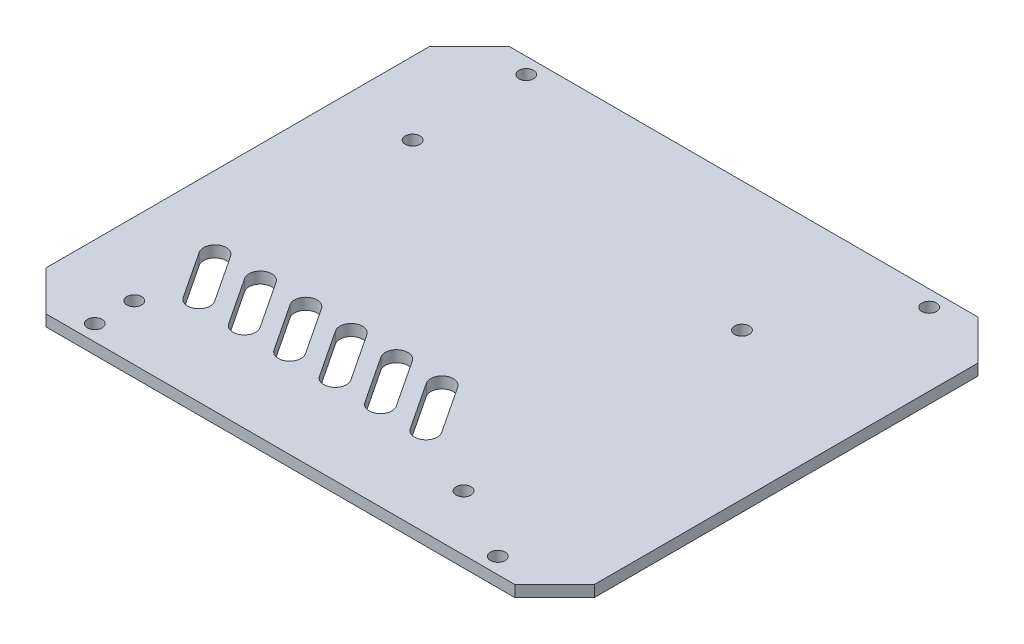
SolidWorks part; units mm, degrees
ref_plane "前视基准面" through (0, 0, 0) normal (0, 0, 1) x (1, 0, 0)
ref_plane "上视基准面" through (0, 0, 0) normal (0, 1, 0) x (1, 0, 0)
ref_plane "右视基准面" through (0, 0, 0) normal (1, 0, 0) x (0, 0, -1)
sketch "草图1" plane through (0, -18.39, 0) normal (0, -1, 0) x (1, 0, 0)
  line L16 (-51.8, -40.2958) -> (-44.7958, -47.3)
  line L17 (-44.7958, -47.3) -> (37.7958, -47.3)
  line L18 (37.7958, -47.3) -> (44.8, -40.2958)
  line L19 (44.8, -40.2958) -> (44.8, 27.2958)
  line L20 (44.8, 27.2958) -> (37.7958, 34.3)
  line L21 (-51.8, 27.2958) -> (-51.8, -40.2958)
  line L22 (37.7958, 34.3) -> (-44.7958, 34.3)
  line L23 (-44.7958, 34.3) -> (-51.8, 27.2958)
  line L24 (-51.8, -40.2958) -> (-44.7958, -47.3)
  line L25 (-44.7958, -47.3) -> (37.7958, -47.3)
  line L26 (37.7958, -47.3) -> (44.8, -40.2958)
  line L27 (44.8, -40.2958) -> (44.8, 27.2958)
  line L28 (44.8, 27.2958) -> (37.7958, 34.3)
  line L29 (-51.8, 27.2958) -> (-51.8, -40.2958)
  line L30 (37.7958, 34.3) -> (-44.7958, 34.3)
  line L31 (-44.7958, 34.3) -> (-51.8, 27.2958)
  dimension "D2" = 96.6
  dimension "D3" = 81.6
  dimension "D1" = 0.2
extrude "凸台-拉伸1" add sketch "草图1" along normal blind 2
sketch "草图2" plane through (0, -20.39, 0) normal (0, -1, 0) x (1, 0, 0)
  circle A0 centre (-39.0116, -24.5) radius 1.3
  circle A1 centre (19, -24.5) radius 1.3
  circle A2 centre (-39.0116, 24.5352) radius 1.3
  circle A3 centre (19, 24.5352) radius 1.3
  dimension "D1" = 2.6
extrude "切除-拉伸1" cut sketch "草图2" against normal up to next
sketch "草图3" plane through (0, -20.39, 0) normal (0, -1, 0) x (1, 0, 0)
  circle A0 centre (32, -44.5) radius 1.3 construction
  circle A1 centre (-39, -44.5) radius 1.3 construction
  circle A2 centre (32, 31.5) radius 1.3 construction
  circle A3 centre (-39, 31.5) radius 1.3 construction
  circle A4 centre (32, -44.5) radius 1.3
  circle A5 centre (-39, -44.5) radius 1.3
  circle A6 centre (32, 31.5) radius 1.3
  circle A7 centre (-39, 31.5) radius 1.3
extrude "切除-拉伸2" cut sketch "草图3" against normal up to next
sketch "草图4" plane through (0, -20.39, 0) normal (0, -1, 0) x (1, 0, 0)
  line L0 (-38.9928, 31.6194) -> (-39.0044, 24.6546) construction
  line L1 (-39.0282, 10.3) -> (-33.5143, 18.6425) construction
  line L2 (-40.6967, 11.4028) -> (-35.1828, 19.7453)
  line L3 (-37.3597, 9.1972) -> (-31.8458, 17.5397)
  line L5 (37.7958, 34.3) -> (-44.7958, 34.3) construction
  line L6 (-31.0282, 10.3) -> (-25.5143, 18.6425) construction
  line L9 (-32.6967, 11.4028) -> (-27.1828, 19.7453)
  line L12 (-29.3597, 9.1972) -> (-23.8458, 17.5397)
  line L15 (-23.0282, 10.3) -> (-17.5143, 18.6425) construction
  line L18 (-24.6967, 11.4028) -> (-19.1828, 19.7453)
  line L21 (-21.3597, 9.1972) -> (-15.8458, 17.5397)
  line L22 (-15.0282, 10.3) -> (-9.5143, 18.6425) construction
  line L23 (-16.6967, 11.4028) -> (-11.1828, 19.7453)
  line L24 (-13.3597, 9.1972) -> (-7.8458, 17.5397)
  line L25 (-7.0282, 10.3) -> (-1.5143, 18.6425) construction
  line L26 (-8.6967, 11.4028) -> (-3.1828, 19.7453)
  line L27 (-5.3597, 9.1972) -> (0.1542, 17.5397)
  line L28 (0.9718, 10.3) -> (6.4857, 18.6425) construction
  line L29 (-0.6967, 11.4028) -> (4.8172, 19.7453)
  line L30 (2.6403, 9.1972) -> (8.1542, 17.5397)
  arc A0 (-40.6967, 11.4028) -> (-37.3597, 9.1972) centre (-39.0282, 10.3) ccw
  arc A1 (-31.8458, 17.5397) -> (-35.1828, 19.7453) centre (-33.5143, 18.6425) ccw
  arc A12 (-32.6967, 11.4028) -> (-29.3597, 9.1972) centre (-31.0282, 10.3) ccw
  arc A13 (-23.8458, 17.5397) -> (-27.1828, 19.7453) centre (-25.5143, 18.6425) ccw
  arc A14 (-24.6967, 11.4028) -> (-21.3597, 9.1972) centre (-23.0282, 10.3) ccw
  arc A15 (-15.8458, 17.5397) -> (-19.1828, 19.7453) centre (-17.5143, 18.6425) ccw
  arc A16 (-16.6967, 11.4028) -> (-13.3597, 9.1972) centre (-15.0282, 10.3) ccw
  arc A17 (-7.8458, 17.5397) -> (-11.1828, 19.7453) centre (-9.5143, 18.6425) ccw
  arc A18 (-8.6967, 11.4028) -> (-5.3597, 9.1972) centre (-7.0282, 10.3) ccw
  arc A19 (0.1542, 17.5397) -> (-3.1828, 19.7453) centre (-1.5143, 18.6425) ccw
  arc A20 (-0.6967, 11.4028) -> (2.6403, 9.1972) centre (0.9718, 10.3) ccw
  arc A21 (8.1542, 17.5397) -> (4.8172, 19.7453) centre (6.4857, 18.6425) ccw
  point P6 (-36.2713, 14.4713)
  point P15 (-28.2713, 14.4713)
  point P22 (-20.2713, 14.4713)
  point P29 (-12.2713, 14.4713)
  point P36 (-4.2713, 14.4713)
  point P43 (3.7287, 14.4713)
  dimension "D1" = 2
  dimension "D2" = 10
  dimension "D3" = 5.5
  dimension "D4" = 12.8
  dimension "D5" = 24
  dimension "D6" = 6
extrude "切除-拉伸3" cut sketch "草图4" against normal up to next
sketch "草图5" plane through (0, -20.39, 0) normal (0, -1, 0) x (1, 0, 0)
sketch_block_instance "块1-1"
sketch_block "块1"
sketch "草图6" plane through (0, -18.39, 0) normal (0, 1, 0) x (1, 0, 0)
  line L0 (-39.0322, 2.6968) -> (-34.8198, 0.2624) construction
  line L1 (-34.177, 0.2624) -> (-29.9873, 2.7014) construction
  line L2 (-29.9828, 3.2622) -> (-34.0539, 5.6966) construction
  line L3 (-29.6682, 9.5398) -> (-30.5435, 10.0367) construction
  line L4 (-30.6757, 9.9592) -> (-30.6757, 7.9487) construction
  line L5 (-30.6301, 7.8712) -> (-29.7548, 7.3788) construction
  line L6 (-29.6226, 7.4564) -> (-29.6226, 9.4623) construction
  line L7 (-33.3108, 9.1249) -> (-33.3108, 8.049) construction
  line L8 (-33.2652, 7.9715) -> (-32.8731, 7.7527) construction
  line L9 (-32.8458, 9.0109) -> (-33.2652, 9.2207) construction
  line L10 (-33.2652, 9.2207) -> (-33.2652, 10.0868) construction
  line L11 (-32.791, 9.8224) -> (-33.2652, 10.0868) construction
  line L12 (-34.3274, 7.7345) -> (-32.823, 6.8819) construction
  line L13 (-34.373, 12.0335) -> (-34.373, 7.8119) construction
  line L14 (-33.3563, 11.6095) -> (-34.2408, 12.111) construction
  line L15 (-33.3108, 10.1644) -> (-33.3108, 11.532) construction
  line L16 (-33.3108, 9.1249) -> (-33.3108, 10.1644) construction
  line L17 (-17.9609, 5.9474) -> (-18.6265, 5.6829) construction
  line L18 (-17.7011, 5.0538) -> (-17.0627, 4.2514) construction
  line L19 (-19.6477, 6.6221) -> (-18.9684, 6.9093) construction
  line L20 (-20.2085, 7.429) -> (-20.9333, 8.3134) construction
  line L21 (-10.1469, 9.1523) -> (-9.7593, 9.1523) construction
  line L22 (-5.5196, 7.1144) -> (-5.5196, 7.7664) construction
  line L23 (-26.0439, 6.3576) -> (-26.0439, 4.2651) construction
  line L24 (-26.0439, 4.2651) -> (-25.2871, 4.2651) construction
  line L25 (-25.2597, 6.3576) -> (-26.0439, 6.3576) construction
  line L26 (-26.7095, 3.7272) -> (-26.7095, 8.979) construction
  line L27 (-26.7095, 8.979) -> (-26.0439, 8.979) construction
  line L28 (-26.0439, 8.979) -> (-26.0439, 6.8956) construction
  line L29 (-26.0439, 6.8956) -> (-25.1731, 6.8956) construction
  line L30 (-25.2096, 3.7272) -> (-26.7095, 3.7272) construction
  line L31 (-33.1558, -0.189) -> (-33.8122, -0.5719) construction
  line L32 (-35.189, -0.5719) -> (-35.8455, -0.189) construction
  line L33 (-35.8455, -0.189) -> (-39.2511, 1.7759) construction
  line L34 (-39.2511, 1.7759) -> (-39.9076, 2.1543) construction
  line L35 (-40.596, 3.3442) -> (-40.596, 8.7967) construction
  line L36 (-39.9076, 9.9866) -> (-39.2511, 10.365) construction
  line L37 (-39.2511, 10.365) -> (-35.8455, 12.3299) construction
  line L38 (-35.8455, 12.3299) -> (-35.189, 12.7128) construction
  line L39 (-33.8122, 12.7128) -> (-33.1558, 12.3299) construction
  line L40 (-33.1558, 12.3299) -> (-29.7503, 10.365) construction
  line L41 (-29.7503, 10.365) -> (-29.0938, 9.9866) construction
  line L42 (-28.4054, 8.7967) -> (-28.4054, 3.3442) construction
  line L43 (-29.0938, 2.1543) -> (-29.7503, 1.7759) construction
  line L44 (-29.7503, 1.7759) -> (-33.1558, -0.189) construction
  line L45 (-5.3737, 8.5687) -> (-5.2826, 8.979) construction
  line L46 (-5.2826, 8.979) -> (-4.2431, 8.979) construction
  line L47 (-4.2431, 8.979) -> (-4.2431, 6.6631) construction
  line L48 (-7.6486, 5.3365) -> (-7.2018, 6.1753) construction
  line L49 (-5.4056, 8.5687) -> (-5.3737, 8.5687) construction
  line L50 (-8.0133, 5.8243) -> (-8.0133, 4.9034) construction
  line L51 (-8.0133, 4.9034) -> (-9.5086, 4.9034) construction
  line L52 (-11.3094, 7.3378) -> (-11.3094, 7.3652) construction
  line L53 (-11.3869, 8.8286) -> (-11.3869, 8.8651) construction
  line L54 (-9.5178, 8.1767) -> (-10.1606, 8.1767) construction
  line L55 (-8.6424, 5.8243) -> (-8.0133, 5.8243) construction
  line L56 (-13.8761, 4.9034) -> (-13.8761, 7.5749) construction
  line L57 (-15.0295, 7.2649) -> (-15.0295, 4.9034) construction
  line L58 (-15.0295, 4.9034) -> (-16.3014, 4.9034) construction
  line L59 (-16.3014, 4.9034) -> (-16.3014, 7.4245) construction
  line L60 (-13.7575, 8.4183) -> (-13.7302, 8.4183) construction
  line L61 (-13.7302, 8.4183) -> (-13.639, 8.979) construction
  line L62 (-13.639, 8.979) -> (-12.5996, 8.979) construction
  line L63 (-12.5996, 8.979) -> (-12.5996, 4.9034) construction
  line L64 (-12.5996, 4.9034) -> (-13.8761, 4.9034) construction
  line L65 (-21.7265, 8.979) -> (-21.7265, 5.0857) construction
  line L66 (-22.3785, 8.979) -> (-21.7265, 8.979) construction
  line L67 (-22.3785, 5.0857) -> (-22.3785, 8.979) construction
  line L68 (-21.7265, 5.0857) -> (-22.3785, 5.0857) construction
  line L69 (-3.4042, 8.979) -> (-2.1368, 8.979) construction
  line L70 (-2.1368, 8.979) -> (-2.1368, 6.6494) construction
  line L71 (-0.8102, 5.9838) -> (-0.596, 4.8851) construction
  line L72 (-2.2508, 5.61) -> (-2.2782, 5.61) construction
  line L73 (-2.2782, 5.61) -> (-2.3648, 4.9034) construction
  line L74 (-2.3648, 4.9034) -> (-3.4042, 4.9034) construction
  line L75 (-3.4042, 4.9034) -> (-3.4042, 8.979) construction
  line L76 (-39.0322, 2.6968) -> (-34.8198, 0.2624)
  line L77 (-34.177, 0.2624) -> (-29.9873, 2.7014)
  line L78 (-29.9828, 3.2622) -> (-34.0539, 5.6966)
  line L79 (-29.6682, 9.5398) -> (-30.5435, 10.0367)
  line L80 (-30.6757, 9.9592) -> (-30.6757, 7.9487)
  line L81 (-30.6301, 7.8712) -> (-29.7548, 7.3788)
  line L82 (-29.6226, 7.4564) -> (-29.6226, 9.4623)
  line L83 (-33.3108, 9.1249) -> (-33.3108, 8.049)
  line L84 (-33.2652, 7.9715) -> (-32.8731, 7.7527)
  line L85 (-32.8458, 9.0109) -> (-33.2652, 9.2207)
  line L86 (-33.2652, 9.2207) -> (-33.2652, 10.0868)
  line L87 (-32.791, 9.8224) -> (-33.2652, 10.0868)
  line L88 (-34.3274, 7.7345) -> (-32.823, 6.8819)
  line L89 (-34.373, 12.0335) -> (-34.373, 7.8119)
  line L90 (-33.3563, 11.6095) -> (-34.2408, 12.111)
  line L91 (-33.3108, 10.1644) -> (-33.3108, 11.532)
  line L92 (-33.3108, 9.1249) -> (-33.3108, 10.1644)
  line L93 (-17.9609, 5.9474) -> (-18.6265, 5.6829)
  line L94 (-17.7011, 5.0538) -> (-17.0627, 4.2514)
  line L95 (-19.6477, 6.6221) -> (-18.9684, 6.9093)
  line L96 (-20.2085, 7.429) -> (-20.9333, 8.3134)
  line L97 (-10.1469, 9.1523) -> (-9.7593, 9.1523)
  line L98 (-5.5196, 7.1144) -> (-5.5196, 7.7664)
  line L99 (-26.0439, 6.3576) -> (-26.0439, 4.2651)
  line L100 (-26.0439, 4.2651) -> (-25.2871, 4.2651)
  line L101 (-25.2597, 6.3576) -> (-26.0439, 6.3576)
  line L102 (-26.7095, 3.7272) -> (-26.7095, 8.979)
  line L103 (-26.7095, 8.979) -> (-26.0439, 8.979)
  line L104 (-26.0439, 8.979) -> (-26.0439, 6.8956)
  line L105 (-26.0439, 6.8956) -> (-25.1731, 6.8956)
  line L106 (-25.2096, 3.7272) -> (-26.7095, 3.7272)
  line L107 (-33.1558, -0.189) -> (-33.8122, -0.5719)
  line L108 (-35.189, -0.5719) -> (-35.8455, -0.189)
  line L109 (-35.8455, -0.189) -> (-39.2511, 1.7759)
  line L110 (-39.2511, 1.7759) -> (-39.9076, 2.1543)
  line L111 (-40.596, 3.3442) -> (-40.596, 8.7967)
  line L112 (-39.9076, 9.9866) -> (-39.2511, 10.365)
  line L113 (-39.2511, 10.365) -> (-35.8455, 12.3299)
  line L114 (-35.8455, 12.3299) -> (-35.189, 12.7128)
  line L115 (-33.8122, 12.7128) -> (-33.1558, 12.3299)
  line L116 (-33.1558, 12.3299) -> (-29.7503, 10.365)
  line L117 (-29.7503, 10.365) -> (-29.0938, 9.9866)
  line L118 (-28.4054, 8.7967) -> (-28.4054, 3.3442)
  line L119 (-29.0938, 2.1543) -> (-29.7503, 1.7759)
  line L120 (-29.7503, 1.7759) -> (-33.1558, -0.189)
  line L121 (-5.3737, 8.5687) -> (-5.2826, 8.979)
  line L122 (-5.2826, 8.979) -> (-4.2431, 8.979)
  line L123 (-4.2431, 8.979) -> (-4.2431, 6.6631)
  line L124 (-7.6486, 5.3365) -> (-7.2018, 6.1753)
  line L125 (-5.4056, 8.5687) -> (-5.3737, 8.5687)
  line L126 (-8.0133, 5.8243) -> (-8.0133, 4.9034)
  line L127 (-8.0133, 4.9034) -> (-9.5086, 4.9034)
  line L128 (-11.3094, 7.3378) -> (-11.3094, 7.3652)
  line L129 (-11.3869, 8.8286) -> (-11.3869, 8.8651)
  line L130 (-9.5178, 8.1767) -> (-10.1606, 8.1767)
  line L131 (-8.6424, 5.8243) -> (-8.0133, 5.8243)
  line L132 (-13.8761, 4.9034) -> (-13.8761, 7.5749)
  line L133 (-15.0295, 7.2649) -> (-15.0295, 4.9034)
  line L134 (-15.0295, 4.9034) -> (-16.3014, 4.9034)
  line L135 (-16.3014, 4.9034) -> (-16.3014, 7.4245)
  line L136 (-13.7575, 8.4183) -> (-13.7302, 8.4183)
  line L137 (-13.7302, 8.4183) -> (-13.639, 8.979)
  line L138 (-13.639, 8.979) -> (-12.5996, 8.979)
  line L139 (-12.5996, 8.979) -> (-12.5996, 4.9034)
  line L140 (-12.5996, 4.9034) -> (-13.8761, 4.9034)
  line L141 (-21.7265, 8.979) -> (-21.7265, 5.0857)
  line L142 (-22.3785, 8.979) -> (-21.7265, 8.979)
  line L143 (-22.3785, 5.0857) -> (-22.3785, 8.979)
  line L144 (-21.7265, 5.0857) -> (-22.3785, 5.0857)
  line L145 (-3.4042, 8.979) -> (-2.1368, 8.979)
  line L146 (-2.1368, 8.979) -> (-2.1368, 6.6494)
  line L147 (-0.8102, 5.9838) -> (-0.596, 4.8851)
  line L148 (-2.2508, 5.61) -> (-2.2782, 5.61)
  line L149 (-2.2782, 5.61) -> (-2.3648, 4.9034)
  line L150 (-2.3648, 4.9034) -> (-3.4042, 4.9034)
  line L151 (-3.4042, 4.9034) -> (-3.4042, 8.979)
  spline S0 degree 3 poles (1947.2043, 259.0221) (-2040.5975, -86.3945) (1971.5647, -86.1046) (-2015.9835, 259.8919) knots -24.014283 -24.014283 -24.014283 -24.014283 31.060476 31.060476 31.060476 31.060476 only from (-34.8198, 0.2624) to (-34.177, 0.2624) construction
  spline S1 degree 3 poles (-178.8618, 1996.4067) (-13.3017, -2002.4803) (85.7628, 2005.1657) (-277.1173, -1980.6649) knots -12.069605 -12.069605 -12.069605 -12.069605 23.053377 23.053377 23.053377 23.053377 only from (-29.9873, 2.7014) to (-29.9828, 3.2622) construction
  spline S2 degree 3 poles (-2011.9647, -280.5218) (1973.0796, 101.2598) (-2042.0834, 101.2623) (1942.99, -280.5143) knots -16.956312 -16.956312 -16.956312 -16.956312 31.955994 31.955994 31.955994 31.955994 only from (-34.0539, 5.6966) to (-34.9429, 5.6966) construction
  spline S3 degree 2 poles (1696.8938, 1005.9909) (-1772.9636, -998.1959) (1692.7429, 1003.6514) knots -19.544322 -19.544322 -19.544322 21.524182 21.524182 21.524182 only from (-34.9429, 5.6966) to (-39.0732, 3.3123) construction
  spline S4 degree 3 poles (312.9236, -1964.6822) (-255.5836, 1997.2947) (39.8207, -2001.4292) (20.6091, 2000.9771) knots -16.033039 -16.033039 -16.033039 -16.033039 19.060221 19.060221 19.060221 19.060221 only from (-39.0732, 3.3123) to (-39.0322, 2.6968) construction
  spline S5 degree 3 poles (1612.1466, 1139.1382) (-173.749, 124.6775) (-29.5451, -1.4055) (-29.5451, 6.2482) (-29.5451, 12.5795) (-131.1047, 41.0713) (891.7703, -1766.7786) knots -20.983072 -20.983072 -20.983072 -20.983072 3 3 3 23.1269 23.1269 23.1269 23.1269 only from (-30.1469, 6.0431) to (-30.1469, 7.1281) construction
  spline S6 degree 3 poles (-1593.6748, -1232.4433) (112.4759, -108.2288) (-30.7532, 14.45) (-30.7532, 6.9321) (-30.7532, 0.2328) (76.6581, -24.0346) (-1002.5668, 1752.6044) knots -22.899222 -22.899222 -22.899222 -22.899222 1 1 1 21.696321 21.696321 21.696321 21.696321 only from (-30.1469, 7.1281) to (-30.1469, 6.0431) construction
  spline S7 degree 3 poles (-1735.267, -1035.1971) (1720.3132, 981.2712) (-1822.079, -884.2768) (1795.5461, 824.5182) knots -24.864003 -24.864003 -24.864003 -24.864003 29.805716 29.805716 29.805716 29.805716 only from (-30.5435, 10.0367) to (-30.6757, 9.9592) construction
  spline S8 degree 3 poles (1803.8452, -787.8206) (-1835.1338, 879.7734) (1736.3613, -937.8925) (-1752.2845, 1025.0132) knots -52.644856 -52.644856 -52.644856 -52.644856 63.422153 63.422153 63.422153 63.422153 only from (-30.6757, 7.9487) to (-30.6301, 7.8712) construction
  spline S9 degree 3 poles (1675.9971, 1050.9308) (-1781.5786, -962.103) (1762.6814, 899.8753) (-1856.6746, -805.2277) knots -20.869425 -20.869425 -20.869425 -20.869425 33.809897 33.809897 33.809897 33.809897 only from (-29.7548, 7.3788) to (-29.6226, 7.4564) construction
  spline S10 degree 3 poles (-1017.153, 1748.416) (898.1967, -1765.8691) (-895.3334, 1815.971) (771.5167, -1822.726) knots -45.73326 -45.73326 -45.73326 -45.73326 46.535072 46.535072 46.535072 46.535072 only from (-29.6226, 9.4623) to (-29.6682, 9.5398) construction
  spline S11 degree 3 poles (1241.4728, -1544.2848) (-126.4363, -19.7603) (-21.5989, 9.5171) (-21.5989, 3.8639) (-21.5989, -3.1211) (-150.7291, 66.7677) (1747.5616, 931.244) knots -20.398043 -20.398043 -20.398043 -20.398043 3 3 3 28.967808 28.967808 28.967808 28.967808 only from (-22.0502, 4.2833) to (-22.0502, 3.44) construction
  spline S12 degree 3 poles (-1791.638, 931.233) (106.6275, 66.7672) (-22.5016, -3.1211) (-22.5016, 3.8639) (-22.5016, 9.5171) (82.3355, -19.7602) (-1285.567, -1544.2778) knots -24.967698 -24.967698 -24.967698 -24.967698 1 1 1 24.398007 24.398007 24.398007 24.398007 only from (-22.0502, 3.44) to (-22.0502, 4.2833) construction
  spline S13 degree 3 poles (953.112, -1731.5311) (-960.0271, 1783.9495) (831.3079, -1798.9714) (-833.3757, 1840.6921) knots -41.715469 -41.715469 -41.715469 -41.715469 50.515238 50.515238 50.515238 50.515238 only from (-33.3108, 8.049) to (-33.2652, 7.9715) construction
  spline S14 degree 3 poles (345.3515, -1953.7628) (-656.074, 2008.4671) (704.4049, -1945.0024) (-795.7723, 1856.1671) knots -18.836401 -18.836401 -18.836401 -18.836401 26.867419 26.867419 26.867419 26.867419 only from (-32.8731, 7.7527) to (-32.0799, 7.9031) construction
  spline S15 degree 3 poles (393.8329, 1947.428) (-1017.3565, -1766.8215) (1294.138, 1559.3727) (-1541.9229, -1298.5467) knots -37.738435 -37.738435 -37.738435 -37.738435 30.849118 30.849118 30.849118 30.849118 only from (-32.0799, 7.9031) to (-32.8458, 9.0109) construction
  spline S16 degree 3 poles (-1970.6267, 490.4514) (1900.3877, -652.3893) (-1909.3139, 822.203) (1735.9268, -921.8099) knots -2.984455 -2.984455 -2.984455 -2.984455 24.908291 24.908291 24.908291 24.908291 only from (-31.0405, 7.315) to (-32.791, 9.8224) construction
  spline S17 degree 3 poles (1301.0551, -1483.1694) (-1380.7778, 1570.3517) (1272.9624, -1585.6466) (-1251.2088, 1591.7607) knots -4.177868 -4.177868 -4.177868 -4.177868 21.267464 21.267464 21.267464 21.267464 only from (-32.823, 6.8819) to (-31.0405, 7.315) construction
  spline S18 degree 3 poles (-426.7908, -1953.0944) (416.9018, 1960.3516) (-543.6183, -1930.3492) (531.9657, 1925.7159) knots -40.574336 -40.574336 -40.574336 -40.574336 54.224541 54.224541 54.224541 54.224541 only from (-34.373, 7.8119) to (-34.3274, 7.7345) construction
  spline S19 degree 3 poles (-1739.7201, -1031.8845) (1717.3311, 982.0362) (-1826.4475, -880.8273) (1792.473, 825.1567) knots -21.867988 -21.867988 -21.867988 -21.867988 32.80886 32.80886 32.80886 32.80886 only from (-34.2408, 12.111) to (-34.373, 12.0335) construction
  spline S20 degree 3 poles (1326.5597, 1477.8337) (-1443.7748, -1422.5109) (1417.5131, 1403.8248) (-1515.2659, -1331.1895) knots -66.611259 -66.611259 -66.611259 -66.611259 68.63044 68.63044 68.63044 68.63044 only from (-33.3108, 11.532) to (-33.3563, 11.6095) construction
  spline S21 degree 3 poles (-1127.9465, 1668.9065) (1205.0665, -1581.8003) (-1320.6139, 1532.1331) (1326.4072, -1474.1074) knots -17.356672 -17.356672 -17.356672 -17.356672 19.212167 19.212167 19.212167 19.212167 only from (-18.6265, 5.6829) to (-19.4334, 5.0857) construction
  spline S22 degree 3 poles (1945.6237, -352.8331) (-1917.2958, 619.5498) (1753.4488, -897.6325) (-1594.6226, 1226.9154) knots -23.773694 -23.773694 -23.773694 -23.773694 31.399142 31.399142 31.399142 31.399142 only from (-19.4334, 5.0857) to (-18.7952, 4.6435) construction
  spline S23 degree 3 poles (-1957.8604, 491.3787) (1905.2875, -332.0334) (-1960.1859, 166.6666) (1980.2936, 44.6676) knots -22.175827 -22.175827 -22.175827 -22.175827 30.019969 30.019969 30.019969 30.019969 only from (-18.7952, 4.6435) to (-17.7011, 5.0538) construction
  spline S24 degree 3 poles (-1996.9289, 274.3391) (2008.3741, -55.5657) (-2041.9478, -141.8187) (1949.9756, 346.3582) knots -14.985955 -14.985955 -14.985955 -14.985955 26.624596 26.624596 26.624596 26.624596 only from (-17.0627, 4.2514) to (-18.7952, 3.5448) construction
  spline S25 degree 3 poles (-959.5674, 1764.5293) (1176.2874, -1603.5878) (-1432.6495, 1427.6748) (1567.7803, -1205.173) knots -7.558703 -7.558703 -7.558703 -7.558703 20.482777 20.482777 20.482777 20.482777 only from (-18.7952, 3.5448) to (-20.7327, 5.1587) construction
  spline S26 degree 3 poles (1924.0493, -458.54) (-2016.5165, 343.495) (1995.4741, -211.501) (-2016.1303, 116.1959) knots -7.852621 -7.852621 -7.852621 -7.852621 24.144848 24.144848 24.144848 24.144848 only from (-20.7327, 5.1587) to (-19.6477, 6.6221) construction
  spline S27 degree 3 poles (615.0637, -1888.8545) (-795.6899, 1841.0297) (868.9978, -1778.6578) (-986.0957, 1757.28) knots -9.138526 -9.138526 -9.138526 -9.138526 27.25787 27.25787 27.25787 27.25787 only from (-18.9684, 6.9093) to (-18.2162, 7.5111) construction
  spline S28 degree 3 poles (215.7009, 1986.9997) (-654.6592, -1923.8751) (894.6606, 1828.6602) (-1110.216, -1665.8008) knots -22.542702 -22.542702 -22.542702 -22.542702 37.658646 37.658646 37.658646 37.658646 only from (-18.2162, 7.5111) to (-18.9137, 7.9761) construction
  spline S29 degree 3 poles (-1605.429, -1208.7716) (1666.7814, 1140.7416) (-1773.5402, -1019.3674) (1765.9801, 905.5471) knots -8.791084 -8.791084 -8.791084 -8.791084 32.386114 32.386114 32.386114 32.386114 only from (-18.9137, 7.9761) to (-20.2085, 7.429) construction
  spline S30 degree 3 poles (1966.5787, -197.5818) (-2051.7497, -0.967) (2002.48, 224.4874) (-1974.8286, -400.794) knots -6.294928 -6.294928 -6.294928 -6.294928 33.756853 33.756853 33.756853 33.756853 only from (-20.9333, 8.3134) to (-18.9411, 9.0793) construction
  spline S31 degree 3 poles (124.1341, -1982.3989) (-457.1442, 1958.1164) (708.8959, -1855.2284) (-1015.0804, 1736.3895) knots 0.697384 0.697384 0.697384 0.697384 28.978211 28.978211 28.978211 28.978211 only from (-18.9411, 9.0793) to (-16.9033, 7.4108) construction
  spline S32 degree 3 poles (-1495.2544, 1354.2838) (1523.5493, -1377.9736) (-1538.1686, 1424.3054) (1353.4505, -1448.6746) knots -4.734801 -4.734801 -4.734801 -4.734801 40.265101 40.265101 40.265101 40.265101 only from (-16.9033, 7.4108) to (-17.9609, 5.9474) construction
  spline S33 degree 3 poles (-1961.8056, -418.0731) (126.6492, -101.6131) (-10.6711, 16.7967) (-10.6711, 6.2847) (-10.6711, -3.9538) (125.3735, 107.9903) (-1932.7785, 547.0377) knots -21.79377 -21.79377 -21.79377 -21.79377 3 3 3 27.67833 27.67833 27.67833 27.67833 only from (-10.156, 6.923) to (-10.156, 5.6556) construction
  spline S34 degree 3 poles (1882.1607, 641.7029) (-158.572, 123.862) (-9.6409, -4.6535) (-9.6409, 6.2847) (-9.6409, 17.5385) (-160.5965, -118.9677) (1923.9331, -488.0552) knots -25.364902 -25.364902 -25.364902 -25.364902 1 1 1 27.543492 27.543492 27.543492 27.543492 only from (-10.156, 5.6556) to (-10.156, 6.923) construction
  spline S35 degree 3 poles (398.3769, -1946.8651) (-621.0655, 1916.7975) (746.5301, -1849.6014) (-860.4662, 1818.6943) knots -20.367991 -20.367991 -20.367991 -20.367991 27.043685 27.043685 27.043685 27.043685 only from (-9.7593, 9.1523) to (-9.1667, 9.4441) construction
  spline S36 degree 3 poles (-1851.6901, 784.2948) (1770.8918, -932.7585) (-1685.1957, 1125.6418) (1512.1872, -1283.8884) knots -14.155704 -14.155704 -14.155704 -14.155704 26.455766 26.455766 26.455766 26.455766 only from (-9.1667, 9.4441) to (-10.0557, 9.8954) construction
  spline S37 degree 3 poles (-1999.7746, -177.9397) (2048.5506, 17.7992) (-2059.7856, 149.4036) (1971.6374, -249.0633) knots -24.53604 -24.53604 -24.53604 -24.53604 22.203045 22.203045 22.203045 22.203045 only from (-10.0557, 9.8954) to (-10.9219, 9.4668) construction
  spline S38 degree 3 poles (335.4233, 1977.3974) (-130.5762, -1935.4278) (-138.8194, 1950.0115) (386.7962, -1948.2187) knots -42.090152 -42.090152 -42.090152 -42.090152 46.007634 46.007634 46.007634 46.007634 only from (-10.9219, 9.4668) to (-10.7304, 9.1021) construction
  spline S39 degree 3 poles (-2000.164, -195.6542) (1968.231, 177.2652) (-1992.5781, -127.132) (1986.8184, 117.9013) knots -23.761314 -23.761314 -23.761314 -23.761314 27.411452 27.411452 27.411452 27.411452 only from (-10.7304, 9.1021) to (-10.1469, 9.1523) construction
  spline S40 degree 3 poles (1900.4815, 611.268) (-1853.5024, -713.4995) (1804.2956, 824.4669) (-1796.5625, -882.5407) knots -25.691977 -25.691977 -25.691977 -25.691977 25.491412 25.491412 25.491412 25.491412 only from (-5.5196, 7.7664) to (-6.135, 8.09) construction
  spline S41 degree 3 poles (-2003.4629, -52.8338) (2017.9029, -136.2777) (-2009.5197, 324.3726) (1939.2706, -450.8338) knots -29.27083 -29.27083 -29.27083 -29.27083 28.779665 28.779665 28.779665 28.779665 only from (-6.135, 8.09) to (-6.5727, 7.739) construction
  spline S42 degree 3 poles (-1965.4656, -395.4958) (1971.7383, 441.6954) (-1983.3474, -426.4496) (1951.4791, 419.1184) knots -18.272249 -18.272249 -18.272249 -18.272249 20.366917 20.366917 20.366917 20.366917 only from (-6.5727, 7.739) to (-5.5196, 7.1144) construction
  spline S43 degree 3 poles (-552.3477, -1916.0072) (39.6444, 1949.1893) (231.1798, -1947.9287) (-488.2476, 1949.0672) knots -16.951569 -16.951569 -16.951569 -16.951569 21.292276 21.292276 21.292276 21.292276 only from (-25.2871, 4.2651) to (-23.9011, 5.2681) construction
  spline S44 degree 3 poles (74.9674, -1978.7796) (-669.1868, 1491.4113) (1220.9961, -1007.5518) (-1925.4997, 576.7533) knots -20.703775 -20.703775 -20.703775 -20.703775 29.911591 29.911591 29.911591 29.911591 only from (-23.9011, 5.2681) to (-25.2597, 6.3576) construction
  spline S45 degree 3 poles (1967.7044, -102.3152) (-2083.6001, -202.2982) (1987.7708, 465.393) (-1913.3422, -643.1952) knots -12.662635 -12.662635 -12.662635 -12.662635 20.708978 20.708978 20.708978 20.708978 only from (-25.1731, 6.8956) to (-23.2401, 5.2681) construction
  spline S46 degree 3 poles (-1462.7137, 1393.5071) (1511.2501, -1404.3078) (-1580.4996, 1407.0991) (1432.7296, -1365.1759) knots -7.615095 -7.615095 -7.615095 -7.615095 23.693651 23.693651 23.693651 23.693651 only from (-23.2401, 5.2681) to (-25.2096, 3.7272) construction
  spline S47 degree 3 poles (-1986.2159, -424.6605) (1872.5149, 650.7296) (-1856.7008, -859.0204) (1668.1443, 1044.8861) knots -40.403395 -40.403395 -40.403395 -40.403395 46.454358 46.454358 46.454358 46.454358 only from (-33.8122, -0.5719) to (-34.5006, -0.7543) construction
  spline S48 degree 3 poles (-1740.3489, 1039.5921) (1790.0962, -854.0172) (-1943.0897, 646.2372) (1918.0006, -420.927) knots -38.373718 -38.373718 -38.373718 -38.373718 48.302597 48.302597 48.302597 48.302597 only from (-34.5006, -0.7543) to (-35.189, -0.5719) construction
  spline S49 degree 3 poles (-754.8971, 1867.8409) (885.9932, -1784.6) (-1157.7277, 1677.1962) (1246.9181, -1524.5355) knots -12.834285 -12.834285 -12.834285 -12.834285 29.798641 29.798641 29.798641 29.798641 only from (-39.9076, 2.1543) to (-40.596, 3.3442) construction
  spline S50 degree 3 poles (1310.7611, 1480.2732) (-1219.4015, -1620.1293) (943.9093, 1763.7167) (-807.2491, -1834.6442) knots -11.169927 -11.169927 -11.169927 -11.169927 32.277267 32.277267 32.277267 32.277267 only from (-40.596, 8.7967) to (-39.9076, 9.9866) construction
  spline S51 degree 3 poles (1829.5545, -704.5958) (-1983.3127, 518.655) (1959.6502, -271.0062) (-2031.7382, 64.4568) knots -28.630568 -28.630568 -28.630568 -28.630568 59.634843 59.634843 59.634843 59.634843 only from (-35.189, 12.7128) to (-34.5006, 12.8952) construction
  spline S52 degree 3 poles (1962.7022, 65.7414) (-2028.2181, -273.3756) (1913.3784, 521.8911) (-1897.0742, -708.4939) knots -29.74703 -29.74703 -29.74703 -29.74703 58.724161 58.724161 58.724161 58.724161 only from (-34.5006, 12.8952) to (-33.8122, 12.7128) construction
  spline S53 degree 3 poles (611.3262, -1882.3455) (-897.4898, 1821.8566) (1049.2417, -1687.0258) (-1295.1838, 1553.5314) knots -2.467628 -2.467628 -2.467628 -2.467628 41.506639 41.506639 41.506639 41.506639 only from (-29.0938, 9.9866) to (-28.4054, 8.7967) construction
  spline S54 degree 3 poles (-1230.5684, -1592.4268) (988.9215, 1738.3623) (-842.904, -1836.9675) (564.0724, 1910.0048) knots -0.095652 -0.095652 -0.095652 -0.095652 42.997123 42.997123 42.997123 42.997123 only from (-28.4054, 3.3442) to (-29.0938, 2.1543) construction
  spline S55 degree 3 poles (-1430.5573, 1407.5659) (1723.1127, -1481.9909) (-1919.6145, 1389.7982) (1763.4855, -917.7581) knots -7.107453 -7.107453 -7.107453 -7.107453 39.300169 39.300169 39.300169 39.300169 only from (-4.2431, 6.6631) to (-5.8934, 4.8031) construction
  spline S56 degree 3 poles (200.3126, 1993.6618) (-113.4143, -2029.6162) (37.9701, 2047.0917) (-46.8978, -1994.2146) knots -24.475698 -24.475698 -24.475698 -24.475698 28.452112 28.452112 28.452112 28.452112 only from (-5.8934, 4.8031) to (-7.6486, 5.3365) construction
  spline S57 degree 3 poles (-1933.6669, -520.0604) (1769.2026, 770.3694) (-1678.914, -975.8177) (1607.9896, 1184.3814) knots -29.345565 -29.345565 -29.345565 -29.345565 33.949512 33.949512 33.949512 33.949512 only from (-7.2018, 6.1753) to (-6.135, 5.8197) construction
  spline S58 degree 3 poles (-1709.7987, 1053.3931) (1749.403, -1046.8479) (-1793.7464, 1008.7473) (1793.1121, -866.6254) knots -20.675466 -20.675466 -20.675466 -20.675466 32.208493 32.208493 32.208493 32.208493 only from (-6.135, 5.8197) to (-5.5196, 6.3394) construction
  spline S59 degree 3 poles (1975.7527, -248.8039) (-1868.9813, 512.6632) (1631.6647, -894.331) (-1295.7423, 1512.4535) knots -12.733532 -12.733532 -12.733532 -12.733532 25.757539 25.757539 25.757539 25.757539 only from (-5.5196, 6.3394) to (-7.7854, 7.8393) construction
  spline S60 degree 3 poles (1042.4421, 1706.8309) (-834.6219, -1820.7719) (589.0356, 1925.2458) (-367.8223, -1955.7065) knots -11.03402 -11.03402 -11.03402 -11.03402 21.264003 21.264003 21.264003 21.264003 only from (-7.7854, 7.8393) to (-6.5727, 9.0793) construction
  spline S61 degree 3 poles (-582.1125, -1906.1013) (523.4678, 1965.3983) (-513.1262, -1956.0805) (513.8823, 1939.9285) knots -17.627726 -17.627726 -17.627726 -17.627726 33.245267 33.245267 33.245267 33.245267 only from (-6.5727, 9.0793) to (-5.4056, 8.5687) construction
  spline S62 degree 3 poles (-1930.5691, 559.3395) (1974.8488, -448.3348) (-2018.9786, 347.7304) (1976.7281, -218.5664) knots -33.500705 -33.500705 -33.500705 -33.500705 55.20773 55.20773 55.20773 55.20773 only from (-9.5086, 4.9034) to (-10.156, 4.8031) construction
  spline S63 degree 3 poles (-1999.2913, 198.6019) (2020.2524, -1.5641) (-2032.1384, -171.0059) (1955.7763, 357.6437) knots -3.872904 -3.872904 -3.872904 -3.872904 23.676976 23.676976 23.676976 23.676976 only from (-10.156, 4.8031) to (-11.8611, 6.2847) construction
  spline S64 degree 3 poles (1939.5115, 440.407) (-1940.4923, -577.4399) (1873.7743, 723.7895) (-1830.7521, -821.4821) knots -8.023341 -8.023341 -8.023341 -8.023341 31.752387 31.752387 31.752387 31.752387 only from (-11.8611, 6.2847) to (-11.3094, 7.3378) construction
  spline S65 degree 3 poles (-1329.9726, 1509.8665) (1428.2205, -1408.3534) (-1547.8279, 1317.3332) (1597.8765, -1177.5524) knots -10.762319 -10.762319 -10.762319 -10.762319 36.904963 36.904963 36.904963 36.904963 only from (-11.3094, 7.3652) to (-11.7608, 8.1265) construction
  spline S66 degree 3 poles (1690.5146, -1041.4074) (-1758.3489, 1014.3497) (1757.9984, -959.3158) (-1776.7351, 948.7003) knots -9.879735 -9.879735 -9.879735 -9.879735 41.23424 41.23424 41.23424 41.23424 only from (-11.7608, 8.1265) to (-11.3869, 8.8286) construction
  spline S67 degree 3 poles (-752.9374, 1842.3255) (1308.8718, -1353.5914) (-1702.759, 958.5145) (1892.0914, -582.47) knots -26.637538 -26.637538 -26.637538 -26.637538 53.487657 53.487657 53.487657 53.487657 only from (-11.3869, 8.8651) to (-11.9659, 9.6674) construction
  spline S68 degree 3 poles (1894.089, -594.3405) (-1996.6922, 519.1508) (2004.2706, -389.5025) (-1990.0486, 289.9866) knots 3.488718 3.488718 3.488718 3.488718 33.266204 33.266204 33.266204 33.266204 only from (-11.9659, 9.6674) to (-10.2563, 10.6932) construction
  spline S69 degree 3 poles (883.5316, -1769.7092) (-1265.933, 1528.3806) (1531.048, -1233.7757) (-1756.2499, 971.1381) knots 2.502912 2.502912 2.502912 2.502912 33.788332 33.788332 33.788332 33.788332 only from (-10.2563, 10.6932) to (-7.9495, 9.2207) construction
  spline S70 degree 3 poles (-1471.0119, 1372.7307) (1578.4938, -1482.6464) (-1566.0618, 1580.68) (1222.054, -1564.0225) knots 0.121158 0.121158 0.121158 0.121158 45.755216 45.755216 45.755216 45.755216 only from (-7.9495, 9.2207) to (-9.5178, 8.1767) construction
  spline S71 degree 3 poles (1988.9699, 46.517) (-2010.5704, -146.5098) (1966.0388, 323.2501) (-1936.5111, -524.1006) knots -22.92357 -22.92357 -22.92357 -22.92357 29.602258 29.602258 29.602258 29.602258 only from (-10.1606, 8.1767) to (-10.7623, 7.9031) construction
  spline S72 degree 3 poles (-533.5031, 1938.1422) (580.6394, -1888.8677) (-675.8787, 1879.566) (733.4353, -1848.486) knots -24.426858 -24.426858 -24.426858 -24.426858 29.596464 29.596464 29.596464 29.596464 only from (-10.7623, 7.9031) to (-10.6347, 7.6159) construction
  spline S73 degree 3 poles (1783.3603, -873.0273) (-1897.0996, 718.9291) (1929.1738, -548.4058) (-1965.9262, 421.9789) knots -49.380783 -49.380783 -49.380783 -49.380783 54.799618 54.799618 54.799618 54.799618 only from (-10.6347, 7.6159) to (-10.156, 7.6889) construction
  spline S74 degree 3 poles (1980.7033, 183.4675) (-2023.5442, -359.0617) (1962.1661, 541.9093) (-1888.572, -672.6294) knots -11.821996 -11.821996 -11.821996 -11.821996 18.874537 18.874537 18.874537 18.874537 only from (-10.156, 7.6889) to (-8.5285, 6.3212) construction
  spline S75 degree 3 poles (-1121.2007, -1655.0713) (1031.1489, 1733.8331) (-972.6532, -1765.1618) (877.4238, 1798.5447) knots -24.892551 -24.892551 -24.892551 -24.892551 35.36044 35.36044 35.36044 35.36044 only from (-8.5285, 6.3212) to (-8.6424, 5.8243) construction
  spline S76 degree 3 poles (1656.0099, -1091.4333) (-1733.7445, 958.5284) (1775.8328, -800.3926) (-1896.9163, 680.7012) knots -21.235065 -21.235065 -21.235065 -21.235065 24.656961 24.656961 24.656961 24.656961 only from (-13.8761, 7.5749) to (-14.5553, 7.9898) construction
  spline S77 degree 3 poles (426.0068, 1957.2742) (-262.0482, -1966.5418) (84.8815, 1999.1955) (-5.2299, -1992.1784) knots -18.599761 -18.599761 -18.599761 -18.599761 21.474642 21.474642 21.474642 21.474642 only from (-14.5553, 7.9898) to (-15.0295, 7.2649) construction
  spline S78 degree 3 poles (-747.2144, 1868.1928) (899.4797, -1926.922) (-1034.2646, 1866.3065) (1043.7125, -1686.9944) knots -15.063115 -15.063115 -15.063115 -15.063115 23.526525 23.526525 23.526525 23.526525 only from (-16.3014, 7.4245) to (-15.034, 9.0793) construction
  spline S79 degree 3 poles (-1430.9478, -1403.3821) (1423.177, 1411.903) (-1498.1835, -1341.8063) (1551.6631, 1251.9189) knots -13.845442 -13.845442 -13.845442 -13.845442 31.313405 31.313405 31.313405 31.313405 only from (-15.034, 9.0793) to (-13.7575, 8.4183) construction
  spline S80 degree 3 poles (1474.4983, 1354.1162) (-1584.5139, -1228.5869) (1669.8836, 1120.5455) (-1739.0959, -982.4011) knots -11.400941 -11.400941 -11.400941 -11.400941 27.863807 27.863807 27.863807 27.863807 only from (-2.1368, 6.6494) to (-1.257, 5.92) construction
  spline S81 degree 3 poles (-1956.5301, 426.4313) (1943.5759, -396.2524) (-1949.6153, 386.5455) (1967.255, -349.6573) knots -19.031705 -19.031705 -19.031705 -19.031705 36.491848 36.491848 36.491848 36.491848 only from (-1.257, 5.92) to (-0.8102, 5.9838) construction
  spline S82 degree 3 poles (1978.5854, -282.24) (-1963.5792, 322.3805) (1959.0024, -335.8715) (-1968.8249, 362.1966) knots -19.114271 -19.114271 -19.114271 -19.114271 38.507502 38.507502 38.507502 38.507502 only from (-0.596, 4.8851) to (-1.0883, 4.8031) construction
  spline S83 degree 3 poles (-1984.9762, 238.8012) (1999.8278, 18.3862) (-1983.2233, -261.3836) (1925.3686, 528.6917) knots -21.685077 -21.685077 -21.685077 -21.685077 21.903976 21.903976 21.903976 21.903976 only from (-1.0883, 4.8031) to (-2.2508, 5.61) construction
  spline S84 degree 3 poles (-34.8198, 0.2624) (-34.6237, 0.1484) (-34.3775, 0.1484) (-34.177, 0.2624) knots 3 3 3 3 4 4 4 4
  spline S85 degree 3 poles (-29.9873, 2.7014) (-29.7731, 2.8245) (-29.7685, 3.1345) (-29.9828, 3.2622) knots 5 5 5 5 6 6 6 6
  spline S86 degree 3 poles (-34.0539, 5.6966) (-34.3274, 5.8562) (-34.6694, 5.8562) (-34.9429, 5.6966) knots 7 7 7 7 8 8 8 8
  spline S87 degree 2 poles (-34.9429, 5.6966) (-39.0641, 3.3169) (-39.0732, 3.3123) knots 0 0 0 1 1 1
  spline S88 degree 3 poles (-39.0732, 3.3123) (-39.2875, 3.1573) (-39.2647, 2.829) (-39.0322, 2.6968) knots 1 1 1 1 2 2 2 2
  spline S89 degree 3 poles (-30.1469, 6.0431) (-29.7958, 5.8425) (-29.5451, 5.9291) (-29.5451, 6.2482) (-29.5451, 6.5628) (-29.7958, 6.9321) (-30.1469, 7.1281) knots 2 2 2 2 3 3 3 4 4 4 4
  spline S90 degree 3 poles (-30.1469, 7.1281) (-30.5024, 7.3333) (-30.7532, 7.2466) (-30.7532, 6.9321) (-30.7532, 6.6084) (-30.5024, 6.2437) (-30.1469, 6.0431) knots 0 0 0 0 1 1 1 2 2 2 2
  spline S91 degree 3 poles (-30.5435, 10.0367) (-30.6028, 10.0686) (-30.6757, 10.0276) (-30.6757, 9.9592) knots 2 2 2 2 3 3 3 3
  spline S92 degree 3 poles (-30.6757, 7.9487) (-30.6757, 7.9168) (-30.6575, 7.8894) (-30.6301, 7.8712) knots 4 4 4 4 5 5 5 5
  spline S93 degree 3 poles (-29.7548, 7.3788) (-29.6956, 7.347) (-29.6226, 7.388) (-29.6226, 7.4564) knots 6 6 6 6 7 7 7 7
  spline S94 degree 3 poles (-29.6226, 9.4623) (-29.6226, 9.4942) (-29.6409, 9.5261) (-29.6682, 9.5398) knots 0 0 0 0 1 1 1 1
  spline S95 degree 3 poles (-22.0502, 4.2833) (-21.7904, 4.2833) (-21.5989, 4.1055) (-21.5989, 3.8639) (-21.5989, 3.5949) (-21.7904, 3.44) (-22.0502, 3.44) knots 2 2 2 2 3 3 3 4 4 4 4
  spline S96 degree 3 poles (-22.0502, 3.44) (-22.3101, 3.44) (-22.5016, 3.5949) (-22.5016, 3.8639) (-22.5016, 4.1055) (-22.3101, 4.2833) (-22.0502, 4.2833) knots 0 0 0 0 1 1 1 2 2 2 2
  spline S97 degree 3 poles (-33.3108, 8.049) (-33.3108, 8.0171) (-33.2926, 7.9852) (-33.2652, 7.9715) knots 4 4 4 4 5 5 5 5
  spline S98 degree 3 poles (-32.8731, 7.7527) (-32.3625, 7.4609) (-32.0799, 7.4564) (-32.0799, 7.9031) knots 6 6 6 6 7 7 7 7
  spline S99 degree 3 poles (-32.0799, 7.9031) (-32.0799, 8.3362) (-32.326, 8.7192) (-32.8458, 9.0109) knots 0 0 0 0 1 1 1 1
  spline S100 degree 3 poles (-31.0405, 7.315) (-31.0405, 8.3682) (-31.8565, 9.2936) (-32.791, 9.8224) knots 10 10 10 10 11 11 11 11
  spline S101 degree 3 poles (-32.823, 6.8819) (-31.8474, 6.3303) (-31.0405, 6.2209) (-31.0405, 7.315) knots 9 9 9 9 10 10 10 10
  spline S102 degree 3 poles (-34.373, 7.8119) (-34.373, 7.78) (-34.3593, 7.7481) (-34.3274, 7.7345) knots 7 7 7 7 8 8 8 8
  spline S103 degree 3 poles (-34.2408, 12.111) (-34.3001, 12.1429) (-34.373, 12.1019) (-34.373, 12.0335) knots 5 5 5 5 6 6 6 6
  spline S104 degree 3 poles (-33.3108, 11.532) (-33.3108, 11.564) (-33.3244, 11.5913) (-33.3563, 11.6095) knots 3 3 3 3 4 4 4 4
  spline S105 degree 3 poles (-18.6265, 5.6829) (-19.0961, 5.496) (-19.4334, 5.382) (-19.4334, 5.0857) knots 1 1 1 1 2 2 2 2
  spline S106 degree 3 poles (-19.4334, 5.0857) (-19.4334, 4.8031) (-19.1918, 4.6435) (-18.7952, 4.6435) knots 2 2 2 2 3 3 3 3
  spline S107 degree 3 poles (-18.7952, 4.6435) (-18.3803, 4.6435) (-18.0521, 4.7848) (-17.7011, 5.0538) knots 3 3 3 3 4 4 4 4
  spline S108 degree 3 poles (-17.0627, 4.2514) (-17.5278, 3.7819) (-18.1797, 3.5448) (-18.7952, 3.5448) knots 5 5 5 5 6 6 6 6
  spline S109 degree 3 poles (-18.7952, 3.5448) (-19.9303, 3.5448) (-20.7327, 4.2651) (-20.7327, 5.1587) knots 6 6 6 6 7 7 7 7
  spline S110 degree 3 poles (-20.7327, 5.1587) (-20.7327, 5.9337) (-20.2085, 6.3987) (-19.6477, 6.6221) knots 7 7 7 7 8 8 8 8
  spline S111 degree 3 poles (-18.9684, 6.9093) (-18.5125, 7.1008) (-18.2162, 7.2011) (-18.2162, 7.5111) knots 9 9 9 9 10 10 10 10
  spline S112 degree 3 poles (-18.2162, 7.5111) (-18.2162, 7.7983) (-18.4395, 7.9761) (-18.9137, 7.9761) knots 10 10 10 10 11 11 11 11
  spline S113 degree 3 poles (-18.9137, 7.9761) (-19.3331, 7.9761) (-19.83, 7.7527) (-20.2085, 7.429) knots 11 11 11 11 12 12 12 12
  spline S114 degree 3 poles (-20.9333, 8.3134) (-20.3817, 8.8195) (-19.634, 9.0793) (-18.9411, 9.0793) knots 13 13 13 13 14 14 14 14
  spline S115 degree 3 poles (-18.9411, 9.0793) (-17.6509, 9.0793) (-16.9033, 8.2998) (-16.9033, 7.4108) knots 14 14 14 14 15 15 15 15
  spline S116 degree 3 poles (-16.9033, 7.4108) (-16.9033, 6.6586) (-17.2998, 6.2118) (-17.9609, 5.9474) knots 15 15 15 15 16 16 16 16
  spline S117 degree 3 poles (-10.156, 6.923) (-10.4477, 6.923) (-10.6711, 6.7087) (-10.6711, 6.2847) (-10.6711, 5.8698) (-10.4477, 5.6556) (-10.156, 5.6556) knots 2 2 2 2 3 3 3 4 4 4 4
  spline S118 degree 3 poles (-10.156, 5.6556) (-9.8551, 5.6556) (-9.6409, 5.8698) (-9.6409, 6.2847) (-9.6409, 6.7087) (-9.8551, 6.923) (-10.156, 6.923) knots 0 0 0 0 1 1 1 2 2 2 2
  spline S119 degree 3 poles (-9.7593, 9.1523) (-9.381, 9.1523) (-9.1667, 9.2024) (-9.1667, 9.4441) knots 4 4 4 4 5 5 5 5
  spline S120 degree 3 poles (-9.1667, 9.4441) (-9.1667, 9.7039) (-9.5314, 9.8954) (-10.0557, 9.8954) knots 5 5 5 5 6 6 6 6
  spline S121 degree 3 poles (-10.0557, 9.8954) (-10.58, 9.8954) (-10.9219, 9.7541) (-10.9219, 9.4668) knots 0 0 0 0 1 1 1 1
  spline S122 degree 3 poles (-10.9219, 9.4668) (-10.9219, 9.3301) (-10.8581, 9.2161) (-10.7304, 9.1021) knots 1 1 1 1 2 2 2 2
  spline S123 degree 3 poles (-10.7304, 9.1021) (-10.5982, 9.1386) (-10.4432, 9.1523) (-10.1469, 9.1523) knots 2 2 2 2 3 3 3 3
  spline S124 degree 3 poles (-5.5196, 7.7664) (-5.7065, 7.967) (-5.8752, 8.09) (-6.135, 8.09) knots 0 0 0 0 1 1 1 1
  spline S125 degree 3 poles (-6.135, 8.09) (-6.3995, 8.09) (-6.5727, 7.9761) (-6.5727, 7.739) knots 1 1 1 1 2 2 2 2
  spline S126 degree 3 poles (-6.5727, 7.739) (-6.5727, 7.4518) (-6.3128, 7.2239) (-5.5196, 7.1144) knots 2 2 2 2 3 3 3 3
  spline S127 degree 3 poles (-25.2871, 4.2651) (-24.3662, 4.2651) (-23.9011, 4.5067) (-23.9011, 5.2681) knots 3 3 3 3 4 4 4 4
  spline S128 degree 3 poles (-23.9011, 5.2681) (-23.9011, 6.0203) (-24.3343, 6.3576) (-25.2597, 6.3576) knots 4 4 4 4 5 5 5 5
  spline S129 degree 3 poles (-25.1731, 6.8956) (-24.0288, 6.8956) (-23.2401, 6.3759) (-23.2401, 5.2681) knots 5 5 5 5 6 6 6 6
  spline S130 degree 3 poles (-23.2401, 5.2681) (-23.2401, 4.1192) (-24.0288, 3.7272) (-25.2096, 3.7272) knots 6 6 6 6 7 7 7 7
  spline S131 degree 3 poles (-33.8122, -0.5719) (-34.0265, -0.6904) (-34.2636, -0.7543) (-34.5006, -0.7543) knots 3 3 3 3 4 4 4 4
  spline S132 degree 3 poles (-34.5006, -0.7543) (-34.7377, -0.7543) (-34.9748, -0.6904) (-35.189, -0.5719) knots 4 4 4 4 5 5 5 5
  spline S133 degree 3 poles (-39.9076, 2.1543) (-40.3315, 2.4005) (-40.596, 2.8564) (-40.596, 3.3442) knots 8 8 8 8 9 9 9 9
  spline S134 degree 3 poles (-40.596, 8.7967) (-40.596, 9.289) (-40.3315, 9.7404) (-39.9076, 9.9866) knots 10 10 10 10 11 11 11 11
  spline S135 degree 3 poles (-35.189, 12.7128) (-34.9748, 12.8359) (-34.7377, 12.8952) (-34.5006, 12.8952) knots 14 14 14 14 15 15 15 15
  spline S136 degree 3 poles (-34.5006, 12.8952) (-34.2636, 12.8952) (-34.0265, 12.8359) (-33.8122, 12.7128) knots 15 15 15 15 16 16 16 16
  spline S137 degree 3 poles (-29.0938, 9.9866) (-28.6652, 9.7404) (-28.4054, 9.289) (-28.4054, 8.7967) knots 19 19 19 19 20 20 20 20
  spline S138 degree 3 poles (-28.4054, 3.3442) (-28.4054, 2.8564) (-28.6652, 2.4005) (-29.0938, 2.1543) knots 21 21 21 21 22 22 22 22
  spline S139 degree 3 poles (-4.2431, 6.6631) (-4.2431, 5.3866) (-4.8403, 4.8031) (-5.8934, 4.8031) knots 11 11 11 11 12 12 12 12
  spline S140 degree 3 poles (-5.8934, 4.8031) (-6.5271, 4.8031) (-7.1106, 5.0173) (-7.6486, 5.3365) knots 0 0 0 0 1 1 1 1
  spline S141 degree 3 poles (-7.2018, 6.1753) (-6.796, 5.9474) (-6.4587, 5.8197) (-6.135, 5.8197) knots 2 2 2 2 3 3 3 3
  spline S142 degree 3 poles (-6.135, 5.8197) (-5.7202, 5.8197) (-5.5469, 6.0112) (-5.5196, 6.3394) knots 3 3 3 3 4 4 4 4
  spline S143 degree 3 poles (-5.5196, 6.3394) (-7.1106, 6.5127) (-7.7854, 6.9777) (-7.7854, 7.8393) knots 4 4 4 4 5 5 5 5
  spline S144 degree 3 poles (-7.7854, 7.8393) (-7.7854, 8.5186) (-7.3249, 9.0793) (-6.5727, 9.0793) knots 5 5 5 5 6 6 6 6
  spline S145 degree 3 poles (-6.5727, 9.0793) (-6.1213, 9.0793) (-5.743, 8.8696) (-5.4056, 8.5687) knots 6 6 6 6 7 7 7 7
  spline S146 degree 3 poles (-9.5086, 4.9034) (-9.6956, 4.835) (-9.9189, 4.8031) (-10.156, 4.8031) knots 9 9 9 9 10 10 10 10
  spline S147 degree 3 poles (-10.156, 4.8031) (-11.0359, 4.8031) (-11.8611, 5.2863) (-11.8611, 6.2847) knots 10 10 10 10 11 11 11 11
  spline S148 degree 3 poles (-11.8611, 6.2847) (-11.8611, 6.7588) (-11.5966, 7.1372) (-11.3094, 7.3378) knots 11 11 11 11 12 12 12 12
  spline S149 degree 3 poles (-11.3094, 7.3652) (-11.5738, 7.5521) (-11.7608, 7.8393) (-11.7608, 8.1265) knots 13 13 13 13 14 14 14 14
  spline S150 degree 3 poles (-11.7608, 8.1265) (-11.7608, 8.4684) (-11.6012, 8.6827) (-11.3869, 8.8286) knots 14 14 14 14 15 15 15 15
  spline S151 degree 3 poles (-11.3869, 8.8651) (-11.7653, 9.0566) (-11.9659, 9.3301) (-11.9659, 9.6674) knots 16 16 16 16 17 17 17 17
  spline S152 degree 3 poles (-11.9659, 9.6674) (-11.9659, 10.3969) (-11.1955, 10.6932) (-10.2563, 10.6932) knots 17 17 17 17 18 18 18 18
  spline S153 degree 3 poles (-10.2563, 10.6932) (-8.8385, 10.6932) (-7.9495, 10.0823) (-7.9495, 9.2207) knots 18 18 18 18 19 19 19 19
  spline S154 degree 3 poles (-7.9495, 9.2207) (-7.9495, 8.4821) (-8.5148, 8.1767) (-9.5178, 8.1767) knots 19 19 19 19 20 20 20 20
  spline S155 degree 3 poles (-10.1606, 8.1767) (-10.5982, 8.1767) (-10.7623, 8.09) (-10.7623, 7.9031) knots 1 1 1 1 2 2 2 2
  spline S156 degree 3 poles (-10.7623, 7.9031) (-10.7623, 7.7664) (-10.7304, 7.7025) (-10.6347, 7.6159) knots 2 2 2 2 3 3 3 3
  spline S157 degree 3 poles (-10.6347, 7.6159) (-10.4569, 7.6661) (-10.2928, 7.6889) (-10.156, 7.6889) knots 3 3 3 3 4 4 4 4
  spline S158 degree 3 poles (-10.156, 7.6889) (-9.2534, 7.6889) (-8.5285, 7.274) (-8.5285, 6.3212) knots 4 4 4 4 5 5 5 5
  spline S159 degree 3 poles (-8.5285, 6.3212) (-8.5285, 6.1251) (-8.5786, 5.9382) (-8.6424, 5.8243) knots 5 5 5 5 6 6 6 6
  spline S160 degree 3 poles (-13.8761, 7.5749) (-14.0903, 7.8758) (-14.2682, 7.9898) (-14.5553, 7.9898) knots 1 1 1 1 2 2 2 2
  spline S161 degree 3 poles (-14.5553, 7.9898) (-14.8791, 7.9898) (-15.0295, 7.8302) (-15.0295, 7.2649) knots 2 2 2 2 3 3 3 3
  spline S162 degree 3 poles (-16.3014, 7.4245) (-16.3014, 8.4411) (-15.923, 9.0793) (-15.034, 9.0793) knots 6 6 6 6 7 7 7 7
  spline S163 degree 3 poles (-15.034, 9.0793) (-14.4779, 9.0793) (-14.0949, 8.8195) (-13.7575, 8.4183) knots 7 7 7 7 8 8 8 8
  spline S164 degree 3 poles (-2.1368, 6.6494) (-1.9226, 6.1115) (-1.5578, 5.92) (-1.257, 5.92) knots 7 7 7 7 8 8 8 8
  spline S165 degree 3 poles (-1.257, 5.92) (-1.0746, 5.92) (-0.9561, 5.9474) (-0.8102, 5.9838) knots 8 8 8 8 9 9 9 9
  spline S166 degree 3 poles (-0.596, 4.8851) (-0.7099, 4.835) (-0.8467, 4.8031) (-1.0883, 4.8031) knots 10 10 10 10 11 11 11 11
  spline S167 degree 3 poles (-1.0883, 4.8031) (-1.4986, 4.8031) (-1.95, 5.0675) (-2.2508, 5.61) knots 0 0 0 0 1 1 1 1
